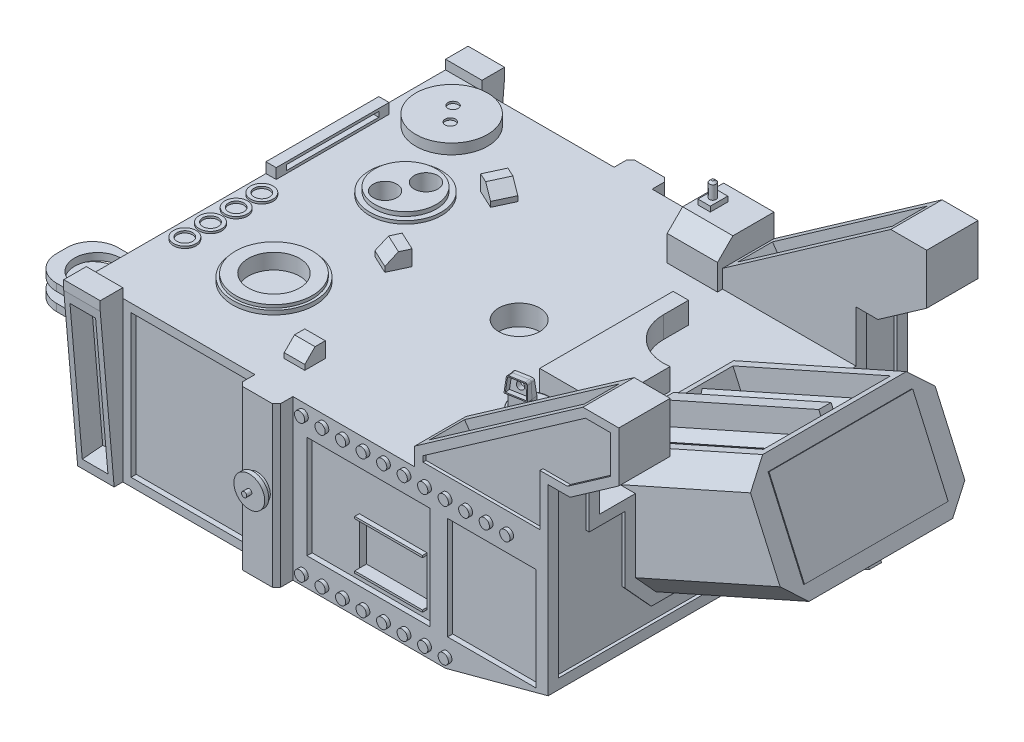
SolidWorks part; units mm, degrees
ref_plane "Ön Düzlem" through (0, 0, 0) normal (0, 0, 1) x (1, 0, 0)
ref_plane "Üst Düzlem" through (0, 0, 0) normal (0, 1, 0) x (1, 0, 0)
ref_plane "Sağ Düzlem" through (0, 0, 0) normal (1, 0, 0) x (0, 0, -1)
sketch "Sketch1" plane through (0, 0, 0) normal (0, 0, 1) x (1, 0, 0)
  line L1 (225, 77.5) -> (-225, 77.5)
  line L2 (225, 77.5) -> (225, -77.5)
  line L3 (225, -77.5) -> (-225, -77.5)
  line L4 (-225, 77.5) -> (-225, -77.5)
  line L5 (225, 77.5) -> (-225, -77.5) construction
  line L6 (225, -77.5) -> (-225, 77.5) construction
  point P0 (0, 0)
  dimension "D1" = 450
  dimension "D2" = 155
extrude "Boss-Extrude1" add sketch "Sketch1" along normal mid plane 350
sketch "Sketch2" plane through (0, 0, 175) normal (0, 0, 1) x (1, 0, 0)
  line L0 (-225, -77.5) -> (225, -77.5) construction
  line L1 (-189.45, -77.5) -> (-225, -77.5)
  line L2 (-189.45, -77.5) -> (-189.45, 86.5)
  line L3 (-189.45, 86.5) -> (-225, 86.5)
  line L4 (-225, -77.5) -> (-225, 86.5)
  line L5 (-225, 77.5) -> (-225, -77.5) construction
  dimension "D1" = 164
  dimension "D2" = 35.55
extrude "Boss-Extrude2" add sketch "Sketch2" along normal blind 22
sketch "Sketch3" plane through (0, 0, 175) normal (0, 0, 1) x (1, 0, 0)
  line L0 (225, 77.5) -> (-189.45, 77.5) construction
  line L1 (-23.725, -77.5) -> (-60.725, -77.5)
  line L2 (-23.725, -77.5) -> (-23.725, 77.5)
  line L3 (-23.725, 77.5) -> (-60.725, 77.5)
  line L4 (-60.725, -77.5) -> (-60.725, 77.5)
  line L5 (-23.725, -77.5) -> (-60.725, 77.5) construction
  line L6 (-23.725, 77.5) -> (-60.725, -77.5) construction
  line L7 (-189.45, 86.5) -> (-225, 86.5) construction
  line L8 (-207.225, 86.5) -> (-207.225, 0) construction
  line L9 (-207.225, 0) -> (0, 0) construction
  point P0 (-42.225, 0)
  dimension "D1" = 165
  dimension "D2" = 37
extrude "Boss-Extrude3" add sketch "Sketch3" along normal blind 16
sketch "Sketch4" plane through (0, 0, 175) normal (0, 0, 1) x (1, 0, 0)
  line L0 (125, -77.5) -> (225, -50.7051)
  line L1 (-23.725, -77.5) -> (225, -77.5) construction
  line L2 (225, -77.5) -> (225, 77.5) construction
  line L3 (225, -50.7051) -> (225, -77.5)
  line L4 (225, -77.5) -> (125, -77.5)
  dimension "D1" = 15
  dimension "D2" = 100
extrude "Cut-Extrude1" cut sketch "Sketch4" against normal through all
sketch "Sketch5" plane through (-225, 0, 0) normal (-1, 0, 0) x (0, 0, 1)
  line L0 (175, 77.5) -> (197, 77.5) construction
  line L1 (197, 86.5) -> (197, -77.5) construction
  line L2 (197, 77.5) -> (183.4393, -77.5)
  line L3 (183.4393, -77.5) -> (197, -77.5)
  line L4 (197, -77.5) -> (197, 77.5)
  dimension "D1" = 5
extrude "Cut-Extrude2" cut sketch "Sketch5" against normal up to surface (35.55 mm away) up to face at (-189.45, 19.1, 183.8)
chamfer "Chamfer1" distance 4 angle 45 2 edges at (-23.725, 0, 191) (-60.725, 0, 191)
sketch "Sketch6" plane through (0, 0, 191) normal (0, 0, 1) x (1, 0, 0)
  line L0 (-42.225, 77.5) -> (-42.225, 0) construction
  line L1 (-27.725, 77.5) -> (-56.725, 77.5) construction
  line L2 (-42.225, 0) -> (0, 0) construction
  circle A0 centre (-42.225, 0) radius 12.5
  dimension "D1" = 25
extrude "Boss-Extrude4" add sketch "Sketch6" along normal blind 4
sketch "Sketch7" plane through (0, 0, 195) normal (0, 0, 1) x (1, 0, 0)
  circle A0 centre (-42.225, 0) radius 15
  dimension "D1" = 30
extrude "Boss-Extrude5" add sketch "Sketch7" along normal blind 4
sketch "Sketch8" plane through (0, 0, 199) normal (0, 0, 1) x (1, 0, 0)
  circle A0 centre (-42.225, 0) radius 2.5
  dimension "D1" = 5
extrude "Boss-Extrude6" add sketch "Sketch8" along normal blind 5
sketch "Sketch9" plane through (0, 0, 175) normal (0, 0, 1) x (1, 0, 0)
  line L0 (50, 0) -> (170, 0) construction
  line L4 (0, 0) -> (50, 0) construction
  line L5 (110, -50) -> (-10, -50)
  line L6 (110, -50) -> (110, 50)
  line L7 (110, 50) -> (-10, 50)
  line L8 (-68.725, -69.5) -> (-68.725, 69.5)
  line L9 (-68.725, 69.5) -> (-181.45, 69.5)
  line L10 (-181.45, 69.5) -> (-181.45, -69.5)
  line L11 (-181.45, -69.5) -> (-68.725, -69.5)
  line L12 (-68.725, -69.5) -> (-68.725, 69.5)
  line L13 (-68.725, 69.5) -> (-181.45, 69.5)
  line L14 (-181.45, 69.5) -> (-181.45, -69.5)
  line L15 (-181.45, -69.5) -> (-68.725, -69.5)
  line L16 (-10, -50) -> (-10, 50)
  line L17 (110, -50) -> (-10, 50) construction
  line L18 (110, 50) -> (-10, -50) construction
  line L20 (213, -50) -> (127, -50)
  line L21 (213, -50) -> (213, 50)
  line L22 (213, 50) -> (127, 50)
  line L23 (127, -50) -> (127, 50)
  line L24 (213, -50) -> (127, 50) construction
  line L25 (213, 50) -> (127, -50) construction
  point P0 (50, 0)
  point P13 (170, 0)
  dimension "D2" = 50
  dimension "D3" = 120
  dimension "D4" = 100
  dimension "D5" = 86
  dimension "D6" = 120
  dimension "D1" = 8
extrude "Cut-Extrude3" cut sketch "Sketch9" against normal blind 5
sketch "Sketch10" plane through (0, 0, 170) normal (0, 0, 1) x (1, 0, 0)
  line L0 (-10, -50) -> (110, -50) construction
  line L1 (102, -40) -> (36, -40)
  line L2 (102, -40) -> (102, 4)
  line L3 (102, 4) -> (36, 4)
  line L4 (36, -40) -> (36, 4)
  line L5 (102, -40) -> (36, 4) construction
  line L6 (102, 4) -> (36, -40) construction
  line L7 (110, -50) -> (110, 50) construction
  point P0 (69, -18)
  dimension "D1" = 10
  dimension "D2" = 44
  dimension "D3" = 8
  dimension "D4" = 66
extrude "Cut-Extrude4" cut sketch "Sketch10" against normal blind 7
sketch "Sketch12" plane through (0, 0, 170) normal (0, 0, 1) x (1, 0, 0)
  line L0 (102, -40) -> (102, 4) construction
  line L1 (36, 4) -> (102, 4)
  line L2 (36, 4) -> (36, 6)
  line L3 (36, 6) -> (102, 6)
  line L4 (102, 4) -> (102, 6)
  line L5 (36, -40) -> (102, -40)
  line L6 (36, -40) -> (36, -42)
  line L7 (36, -42) -> (102, -42)
  line L8 (102, -40) -> (102, -42)
  line L9 (102, -40) -> (102, 4) construction
  dimension "D1" = 2
  dimension "D2" = 2
extrude "Boss-Extrude7" add sketch "Sketch12" along normal blind 4.5
sketch "Sketch13" plane through (0, -16.5156, 188.7747) normal (0, -0.0872, 0.9962) x (1, 0, 0)
  line L0 (-207.225, 94.3748) -> (-207.225, -61.2173) construction
  line L1 (-219.725, 85.5787) -> (-194.725, 85.5787)
  line L2 (-219.725, 85.5787) -> (-219.725, -52.4213)
  line L3 (-219.725, -52.4213) -> (-194.725, -52.4213)
  line L4 (-194.725, 85.5787) -> (-194.725, -52.4213)
  line L5 (-189.45, 94.3748) -> (-225, 94.3748) construction
  line L6 (-189.45, -61.2173) -> (-225, -61.2173) construction
  line L7 (-225, 16.5787) -> (-189.45, 16.5787) construction
  line L8 (-225, 94.3748) -> (-225, -61.2173) construction
  line L9 (-189.45, -61.2173) -> (-189.45, 94.3748) construction
  point P10 (-207.225, 85.5787)
  point P17 (-219.725, 16.5787)
  dimension "D1" = 25
  dimension "D2" = 138
extrude "Cut-Extrude5" cut sketch "Sketch13" against normal blind 20
mirror "Mirror1" about plane through (0, 0, 0) normal (0, 0, 1) of "Cut-Extrude5", "Boss-Extrude7", "Cut-Extrude4", "Cut-Extrude3", "Boss-Extrude6", "Boss-Extrude5", "Boss-Extrude4", "Chamfer1", "Cut-Extrude2", "Boss-Extrude3", "Boss-Extrude2"
sketch "Sketch14" plane through (-225, 0, 0) normal (-1, 0, 0) x (0, 0, 1)
  line L0 (0, 0) -> (-190.2196, 0) construction
  line L1 (-197, 77.5) -> (-183.4393, -77.5) construction
  line L2 (0, 0) -> (190.2196, 0) construction
  line L3 (197, 77.5) -> (183.4393, -77.5) construction
  line L5 (-65, 60) -> (-170, 60)
  line L6 (-65, 60) -> (-65, -60)
  line L7 (-65, -60) -> (-170, -60)
  line L8 (-170, 60) -> (-170, -60)
  line L9 (-65, 60) -> (-170, -60) construction
  line L10 (-65, -60) -> (-170, 60) construction
  point P5 (-117.5, 0)
  dimension "D1" = 105
  dimension "D2" = 120
  dimension "D3" = 170
extrude "Cut-Extrude6" cut sketch "Sketch14" against normal blind 15
sketch "Sketch15" plane through (-210, 0, 0) normal (-1, 0, 0) x (0, 0, 1)
  line L0 (-164.8939, -60) -> (-65, -60) construction
  line L1 (-170, 60) -> (-170, -60) construction
  circle A0 centre (-143, -5) radius 7.5
  dimension "D3" = 15
  dimension "D1" = 55
  dimension "D2" = 27
extrude "Boss-Extrude8" add sketch "Sketch15" along normal blind 15
sketch "Sketch16" plane through (-225, 0, 0) normal (-1, 0, 0) x (0, 0, 1)
  line L0 (0, 0) -> (99, 0) construction
  circle A0 centre (99, 0) radius 48.5
  dimension "D2" = 97
  dimension "D1" = 99
extrude "Boss-Extrude9" add sketch "Sketch16" along normal blind 10
sketch "Sketch17" plane through (-235, 0, 0) normal (-1, 0, 0) x (0, 0, 1)
  circle A0 centre (99, 0) radius 35
  dimension "D1" = 70
extrude "Boss-Extrude11" add sketch "Sketch17" along normal blind 5 contours A0
sketch "Sketch18" plane through (-240, 0, 0) normal (-1, 0, 0) x (0, 0, 1)
  line L0 (0, 0) -> (134, 0) construction
  line L1 (99, 0) -> (99, 35) construction
  line L2 (129, 5) -> (69, 5)
  line L3 (129, 5) -> (129, 12)
  line L4 (129, 12) -> (69, 12)
  line L5 (69, 5) -> (69, 12)
  line L6 (129, 5) -> (69, 12) construction
  line L7 (129, 12) -> (69, 5) construction
  line L8 (129, -12) -> (69, -12)
  line L9 (69, -5) -> (69, -12)
  line L10 (129, -5) -> (69, -5)
  line L11 (129, -5) -> (129, -12)
  circle A0 centre (99, 0) radius 35 construction
  circle A1 centre (99, 0) radius 35 construction
  point P6 (99, 8.5)
  dimension "D1" = 7
  dimension "D2" = 60
  dimension "D3" = 5
extrude "Boss-Extrude12" add sketch "Sketch18" along normal blind 85
fillet "Fillet4" radius 25 4 edges at (-325, -8.5, 129) (-325, 8.5, 129) (-325, 8.5, 69) (-325, -8.5, 69)
sketch "Sketch19" plane through (0, -12, 0) normal (0, -1, 0) x (1, 0, 0)
  line L0 (-240, 99) -> (-325, 99) construction
  line L1 (-240, 69) -> (-240, 129) construction
  line L2 (-325, 94) -> (-325, 104) construction
  line L3 (-240, 134) -> (-240, 64) construction
  circle A0 centre (-290, 99) radius 22.5
  dimension "D2" = 45
  dimension "D1" = 50
extrude "Cut-Extrude7" cut sketch "Sketch19" against normal blind 85
sketch "Sketch20" plane through (0, 77.5, 0) normal (0, 1, 0) x (1, 0, 0)
  line L0 (-225, -175) -> (-225, 175) construction
  line L1 (-225, 110) -> (-215, 110)
  line L2 (-225, 110) -> (-225, 0)
  line L3 (-225, 0) -> (-215, 0)
  line L4 (-215, 110) -> (-215, 0)
  dimension "D1" = 110
  dimension "D2" = 10
extrude "Boss-Extrude13" add sketch "Sketch20" along normal blind 10
sketch "Sketch21" plane through (-225, 0, 0) normal (-1, 0, 0) x (0, 0, 1)
  line L0 (-110, 82.5) -> (0, 82.5) construction
  line L1 (-110, 87.5) -> (-110, 77.5) construction
  line L2 (0, 87.5) -> (0, 77.5) construction
  line L4 (-10, 85) -> (-100, 85)
  line L5 (-10, 85) -> (-10, 80)
  line L6 (-10, 80) -> (-100, 80)
  line L7 (-100, 85) -> (-100, 80)
  line L8 (-10, 85) -> (-100, 80) construction
  line L9 (-10, 80) -> (-100, 85) construction
  point P6 (-55, 82.5)
  dimension "D1" = 90
  dimension "D2" = 5
extrude "Cut-Extrude8" cut sketch "Sketch21" against normal blind 10
sketch "Sketch22" plane through (-225, 0, 0) normal (-1, 0, 0) x (0, 0, 1)
  line L1 (47.5, 0.9) -> (-47.5, 0.9)
  line L2 (47.5, 0.9) -> (47.5, -31.1)
  line L3 (47.5, -31.1) -> (-47.5, -31.1)
  line L4 (-47.5, 0.9) -> (-47.5, -31.1)
  line L5 (47.5, 0.9) -> (-47.5, -31.1) construction
  line L6 (47.5, -31.1) -> (-47.5, 0.9) construction
  point P0 (0, -15.1)
  dimension "D1" = 95
  dimension "D2" = 32
  dimension "D3" = 15.1
extrude "Cut-Extrude9" cut sketch "Sketch22" against normal blind 5
sketch "Sketch23" plane through (0, 77.5, 0) normal (0, 1, 0) x (1, 0, 0)
  line L0 (-42.225, 204) -> (-42.225, 0) construction
  line L1 (-39.725, 204) -> (-44.725, 204) construction
  line L2 (-42.225, 0) -> (21.775, 0) construction
  circle A0 centre (21.775, 0) radius 20
  dimension "D2" = 40
  dimension "D1" = 64
extrude "Cut-Extrude10" cut sketch "Sketch23" against normal blind 20
sketch "Sketch24" plane through (0, 0, 0) normal (0, 0, 1) x (1, 0, 0)
  line L0 (0, 50) -> (99, 50) construction
  line L1 (110, 50) -> (-10, 50) construction
  line L2 (0, 0) -> (0, 50) construction
  line L3 (99, 50) -> (144.1478, -51.4035)
  line L4 (144.1478, -51.4035) -> (374.1478, 50.9991)
  line L5 (374.1478, 50.9991) -> (329, 152.4026)
  line L6 (329, 152.4026) -> (99, 50)
  dimension "D1" = 99
  dimension "D2" = 111
  dimension "D3" = 156
  dimension "D4" = 230
extrude "Boss-Extrude14" add sketch "Sketch24" along normal mid plane 180
chamfer "Chamfer3" distance 20 angle 45 4 edges at (299.5739, 17.7966, 90) (244.883, 114.9513, 90) (299.5739, 17.7966, -90) (244.883, 114.9513, -90)
sketch "Sketch25" plane through (-2.2006, 4.9426, 0) normal (-0.4067, 0.9135, 0) x (0.9135, 0.4067, 0)
  line L8 (186.3891, 62) -> (186.3891, -62)
  line L9 (186.3891, -62) -> (354.5442, -62)
  line L10 (354.5442, -62) -> (354.5442, 62)
  line L11 (354.5442, 62) -> (186.3891, 62)
  line L12 (186.3891, 62) -> (186.3891, -62)
  line L13 (186.3891, -62) -> (354.5442, -62)
  line L14 (354.5442, -62) -> (354.5442, 62)
  line L15 (354.5442, 62) -> (186.3891, 62)
  dimension "D1" = 8
extrude "Cut-Extrude11" cut sketch "Sketch25" against normal up to surface (111 mm away) up to face at (299.5739, 17.7966, 0)
sketch "Sketch26" plane through (170.275, 75.8113, 0) normal (0.9135, 0.4067, 0) x (0, 0, -1)
  line L0 (0, 5.4103) -> (0, -105.5897) construction
  line L1 (62, 5.4103) -> (-62, 5.4103) construction
  line L4 (-62, -105.5897) -> (62, -105.5897) construction
  circle A0 centre (0, -50.0897) radius 32.5
  dimension "D1" = 65
extrude "Boss-Extrude15" add sketch "Sketch26" along normal up to surface (168.155 mm away) up to face at (344.2655, 98.4469, 0)
ref_plane "Plane1" through (-2.2006, 4.9426, 0) normal (-0.4067, 0.9135, 0) x (0.9135, 0.4067, 0)
sketch "Sketch27" plane through (-2.2006, 4.9426, 0) normal (-0.4067, 0.9135, 0) x (0.9135, 0.4067, 0)
  line L0 (186.3891, 0) -> (354.5442, 0) construction
  line L1 (186.3891, -32.5) -> (186.3891, 32.5) construction
  line L2 (354.5442, -62) -> (354.5442, 62) construction
  line L3 (270.4667, 0) -> (270.4667, -62) construction
  line L4 (186.3891, -62) -> (354.5442, -62) construction
  line L6 (354.5442, -6) -> (186.3891, -6)
  line L7 (354.5442, -6) -> (354.5442, 6)
  line L8 (354.5442, 6) -> (186.3891, 6)
  line L9 (186.3891, -6) -> (186.3891, 6)
  line L10 (354.5442, -6) -> (186.3891, 6) construction
  line L11 (354.5442, 6) -> (186.3891, -6) construction
  dimension "D1" = 12
extrude "Boss-Extrude17" add sketch "Sketch27" along normal blind 5 and the other way up to surface contours L6 L9 L8 L7 other way up to face at (203.8672, 0.3619, 0)
pattern_circular "CirPattern1" count 10 over 360 about axis through (20.3733, -45.7592, 0) along (0.9135, 0.4067, 0) of "Boss-Extrude17"
sketch "Sketch28" plane through (331.2006, 147.46, 0) normal (0.9135, 0.4067, 0) x (0, 0, -1)
  line L0 (-90, -50.0897) -> (90, -50.0897) construction
  line L1 (-90, -85.5897) -> (-90, -14.5897) construction
  line L2 (90, -85.5897) -> (90, -14.5897) construction
  line L3 (0, 5.4103) -> (0, -105.5897) construction
  line L4 (6, 5.4103) -> (-6, 5.4103) construction
  line L5 (-70, -105.5897) -> (70, -105.5897) construction
  line L7 (70, -92.5897) -> (-70, -92.5897)
  line L8 (70, -92.5897) -> (70, -7.5897)
  line L9 (70, -7.5897) -> (-70, -7.5897)
  line L10 (-70, -92.5897) -> (-70, -7.5897)
  line L11 (70, -92.5897) -> (-70, -7.5897) construction
  line L12 (70, -7.5897) -> (-70, -92.5897) construction
  point P12 (0, -50.0897)
  dimension "D1" = 140
  dimension "D2" = 85
extrude "Boss-Extrude18" add sketch "Sketch28" along normal blind 1
sketch "Sketch29" plane through (0, 0, 175) normal (0, 0, 1) x (1, 0, 0)
  line L0 (-23.725, 67) -> (225, 67) construction
  line L1 (-23.725, -77.5) -> (-23.725, 77.5) construction
  line L2 (225, -50.7051) -> (225, 77.5) construction
  line L3 (225, 77.5) -> (-23.725, 77.5) construction
  line L4 (-27.725, -77.5) -> (-27.725, 77.5) construction
  line L5 (-13.725, 67) -> (-13.725, -67) construction
  line L6 (-23.725, -67) -> (164.1865, -67) construction
  line L7 (225, -50.7051) -> (125, -77.5) construction
  line L8 (-23.725, -77.5) -> (125, -77.5) construction
  circle A0 centre (-13.725, 67) radius 5
  circle A1 centre (6.275, 67) radius 5
  circle A2 centre (26.275, 67) radius 5
  circle A3 centre (46.275, 67) radius 5
  circle A4 centre (66.275, 67) radius 5
  circle A5 centre (86.275, 67) radius 5
  circle A6 centre (106.275, 67) radius 5
  circle A7 centre (126.275, 67) radius 5
  circle A8 centre (146.275, 67) radius 5
  circle A9 centre (166.275, 67) radius 5
  circle A10 centre (186.275, 67) radius 5
  circle A11 centre (-13.725, -67) radius 5
  circle A12 centre (6.275, -67) radius 5
  circle A13 centre (26.275, -67) radius 5
  circle A14 centre (46.275, -67) radius 5
  circle A15 centre (66.275, -67) radius 5
  circle A16 centre (86.275, -67) radius 5
  circle A17 centre (106.275, -67) radius 5
  circle A18 centre (126.275, -67) radius 5
  dimension "D3" = 10
  dimension "D7" = 10
  dimension "D1" = 10.5
  dimension "D2" = 14
  dimension "D5" = 20
  dimension "D6" = 10.5
  dimension "D9" = 20
  dimension "D4" = 11
  dimension "D8" = 8
extrude "Boss-Extrude19" add sketch "Sketch29" along normal blind 3.5
mirror "Mirror2" about plane through (0, 0, 0) normal (0, 0, 1) of "Boss-Extrude19"
sketch "Sketch30" plane through (-225, 0, 0) normal (-1, 0, 0) x (0, 0, 1)
  line L0 (195.6877, 62.5) -> (-40.6, 62.5) construction
  line L1 (197, 77.5) -> (183.4393, -77.5) construction
  line L2 (175, 77.5) -> (0, 77.5) construction
  line L3 (197, 86.5) -> (197, 77.5) construction
  circle A0 centre (175.4, 62.5) radius 5.5
  circle A1 centre (157.4, 62.5) radius 5.5
  circle A2 centre (139.4, 62.5) radius 5.5
  circle A3 centre (121.4, 62.5) radius 5.5
  circle A4 centre (103.4, 62.5) radius 5.5
  circle A5 centre (85.4, 62.5) radius 5.5
  circle A6 centre (67.4, 62.5) radius 5.5
  circle A7 centre (49.4, 62.5) radius 5.5
  circle A8 centre (31.4, 62.5) radius 5.5
  circle A9 centre (13.4, 62.5) radius 5.5
  circle A10 centre (-4.6, 62.5) radius 5.5
  circle A11 centre (-22.6, 62.5) radius 5.5
  circle A12 centre (-40.6, 62.5) radius 5.5
  dimension "D3" = 11
  dimension "D1" = 15
  dimension "D2" = 21.6
  dimension "D5" = 18
  dimension "D4" = 13
extrude "Boss-Extrude20" add sketch "Sketch30" along normal blind 2.5
sketch "Sketch31" plane through (0, 0, 175) normal (0, 0, 1) x (1, 0, 0)
  line L0 (225, 77.5) -> (95, 77.5)
  line L1 (225, 77.5) -> (-23.725, 77.5) construction
  line L2 (95, 77.5) -> (95, 95.0521)
  line L3 (95, 95.0521) -> (258.8304, 209.7674)
  line L4 (258.8304, 209.7674) -> (293.8304, 209.7674)
  line L5 (293.8304, 209.7674) -> (293.8304, 160.7674)
  line L6 (293.8304, 160.7674) -> (246.3196, 127.5)
  line L7 (246.3196, 127.5) -> (225, 127.5)
  line L8 (225, 127.5) -> (225, 77.5)
  dimension "D1" = 200
  dimension "D2" = 35
  dimension "D3" = 50
  dimension "D4" = 58
  dimension "D5" = 49
  dimension "D6" = 130
  dimension "D7" = 145
extrude "Boss-Extrude21" add sketch "Sketch31" against normal blind 50
sketch "Sketch32" plane through (-13.4059, 19.1455, 0) normal (-0.5736, 0.8192, 0) x (0.8192, 0.5736, 0)
  line L8 (140.3391, -167) -> (324.3391, -167)
  line L9 (324.3391, -167) -> (324.3391, -133)
  line L10 (324.3391, -133) -> (140.3391, -133)
  line L11 (140.3391, -133) -> (140.3391, -167)
  line L12 (140.3391, -167) -> (324.3391, -167)
  line L13 (324.3391, -167) -> (324.3391, -133)
  line L14 (324.3391, -133) -> (140.3391, -133)
  line L15 (140.3391, -133) -> (140.3391, -167)
  dimension "D1" = 8
extrude "Cut-Extrude12" cut sketch "Sketch32" against normal blind 25
sketch "Sketch33" plane through (0, 0, 175) normal (0, 0, 1) x (1, 0, 0)
  line L0 (95, 77.5) -> (95, 95.0521) construction
  line L1 (95, 95.0521) -> (258.8304, 209.7674) construction
  line L2 (258.8304, 209.7674) -> (293.8304, 209.7674) construction
  line L3 (293.8304, 209.7674) -> (293.8304, 160.7674) construction
  line L4 (293.8304, 160.7674) -> (246.3196, 127.5) construction
  line L5 (246.3196, 127.5) -> (293.8304, 160.7674) construction
  line L6 (246.3196, 127.5) -> (225, 127.5) construction
  line L7 (225, 127.5) -> (225, 77.5) construction
  line L8 (225, -50.7051) -> (225, 127.5) construction
  line L9 (225, 77.5) -> (95, 77.5) construction
  line L10 (103, 90.8876) -> (261.3528, 201.7674)
  line L11 (261.3528, 201.7674) -> (285.8304, 201.7674)
  line L12 (285.8304, 201.7674) -> (285.8304, 164.932)
  line L13 (285.8304, 164.932) -> (243.7972, 135.5)
  line L14 (243.7972, 135.5) -> (217, 135.5)
  line L15 (217, 135.5) -> (217, 85.5)
  line L16 (217, 85.5) -> (103, 85.5)
  line L17 (103, 85.5) -> (103, 90.8876)
  dimension "D1" = 8
extrude "Cut-Extrude13" cut sketch "Sketch33" against normal blind 3
mirror "Mirror3" about plane through (0, 0, 0) normal (0, 0, 1) of "Boss-Extrude21", "Cut-Extrude12", "Cut-Extrude13"
sketch "Sketch34" plane through (225, 0, 0) normal (1, 0, 0) x (0, 0, -1)
  line L40 (16, -30.879) -> (-16, -30.879)
  line L41 (-16, -30.879) -> (-16, -25.4058)
  line L42 (-16, -25.4058) -> (-62, -25.4058)
  line L43 (-62, -25.4058) -> (-74.4092, -25.4058)
  line L44 (-74.4092, -25.4058) -> (-100, 2.6069)
  line L45 (-100, 2.6069) -> (-100, 67.5)
  line L46 (-100, 67.5) -> (-135, 67.5)
  line L47 (-135, 67.5) -> (-135, 117.5)
  line L48 (-135, 117.5) -> (-165, 117.5)
  line L49 (-165, 117.5) -> (-165, -40.7051)
  line L50 (-165, -40.7051) -> (165, -40.7051)
  line L51 (165, -40.7051) -> (165, 117.5)
  line L52 (165, 117.5) -> (135, 117.5)
  line L53 (135, 117.5) -> (135, 67.5)
  line L54 (135, 67.5) -> (100, 67.5)
  line L55 (100, 67.5) -> (100, 2.6069)
  line L56 (100, 2.6069) -> (74.4092, -25.4058)
  line L57 (74.4092, -25.4058) -> (62, -25.4058)
  line L58 (62, -25.4058) -> (16, -25.4058)
  line L59 (16, -25.4058) -> (16, -30.879)
  line L60 (16, -30.879) -> (-16, -30.879)
  line L61 (-16, -30.879) -> (-16, -25.4058)
  line L62 (-16, -25.4058) -> (-62, -25.4058)
  line L63 (-62, -25.4058) -> (-74.4092, -25.4058)
  line L64 (-74.4092, -25.4058) -> (-100, 2.6069)
  line L65 (-100, 2.6069) -> (-100, 67.5)
  line L66 (-100, 67.5) -> (-135, 67.5)
  line L67 (-135, 67.5) -> (-135, 117.5)
  line L68 (-135, 117.5) -> (-165, 117.5)
  line L69 (-165, 117.5) -> (-165, -40.7051)
  line L70 (-165, -40.7051) -> (165, -40.7051)
  line L71 (165, -40.7051) -> (165, 117.5)
  line L72 (165, 117.5) -> (135, 117.5)
  line L73 (135, 117.5) -> (135, 67.5)
  line L74 (135, 67.5) -> (100, 67.5)
  line L75 (100, 67.5) -> (100, 2.6069)
  line L76 (100, 2.6069) -> (74.4092, -25.4058)
  line L77 (74.4092, -25.4058) -> (62, -25.4058)
  line L78 (62, -25.4058) -> (16, -25.4058)
  line L79 (16, -25.4058) -> (16, -30.879)
  dimension "D1" = 10
extrude "Cut-Extrude14" cut sketch "Sketch34" against normal blind 3
sketch "Sketch35" plane through (0, 77.5, 0) normal (0, 1, 0) x (1, 0, 0)
  line L0 (-225, 110) -> (-225, 0) construction
  circle A0 centre (-175, 131) radius 35
  dimension "D3" = 70
  dimension "D1" = 50
  dimension "D2" = 44
extrude "Boss-Extrude22" add sketch "Sketch35" along normal blind 10
sketch "Sketch36" plane through (0, 87.5, 0) normal (0, 1, 0) x (1, 0, 0)
  line L0 (-210, 131) -> (-140, 131) construction
  line L1 (-175, 96) -> (-175, 166) construction
  circle A0 centre (-175, 131) radius 35 construction
  circle A1 centre (-175, 131) radius 35 construction
  circle A2 centre (-181.33, 138.66) radius 5
  circle A3 centre (-168.67, 123.34) radius 5
  dimension "D2" = 6.33
  dimension "D4" = 7.66
  dimension "D5" = 10
  dimension "D1" = 7.66
  dimension "D3" = 6.33
extrude "Cut-Extrude15" cut sketch "Sketch36" against normal blind 2
sketch "Sketch37" plane through (0, 77.5, 0) normal (0, 1, 0) x (1, 0, 0)
  line L1 (95, 175) -> (46, 175)
  line L2 (95, 175) -> (95, 120)
  line L3 (95, 120) -> (46, 120)
  line L4 (46, 175) -> (46, 120)
  dimension "D1" = 49
  dimension "D2" = 55
extrude "Boss-Extrude23" add sketch "Sketch37" along normal blind 40 contours L3 L4 L1 L2
chamfer "Chamfer4" distance 15 angle 45 1 edges at (70.5, 117.5, -120)
sketch "Sketch38" plane through (0, 117.5, 0) normal (0, 1, 0) x (1, 0, 0)
  line L0 (46, 175) -> (46, 120) construction
  line L1 (64, 161) -> (52, 161)
  line L2 (64, 161) -> (64, 144)
  line L3 (64, 144) -> (52, 144)
  line L4 (52, 161) -> (52, 144)
  line L5 (64, 161) -> (52, 144) construction
  line L6 (64, 144) -> (52, 161) construction
  line L8 (46, 175) -> (-23.725, 175) construction
  point P0 (58, 152.5)
  dimension "D1" = 12
  dimension "D2" = 17
  dimension "D3" = 6
  dimension "D4" = 14
extrude "Boss-Extrude24" add sketch "Sketch38" along normal blind 5
sketch "Sketch39" plane through (0, 122.5, 0) normal (0, 1, 0) x (1, 0, 0)
  line L0 (52, 152.5) -> (64, 152.5) construction
  line L1 (52, 161) -> (52, 144) construction
  line L2 (64, 144) -> (64, 161) construction
  line L3 (58, 161) -> (58, 144) construction
  line L4 (64, 161) -> (52, 161) construction
  line L5 (52, 144) -> (64, 144) construction
  circle A0 centre (58, 152.5) radius 3.25
  dimension "D1" = 6.5
extrude "Boss-Extrude25" add sketch "Sketch39" along normal blind 15
chamfer "Chamfer5" distance 2 angle 45 1 edges at (58, 137.5, -149.25)
sketch "Sketch40" plane through (0, 77.5, 0) normal (0, 1, 0) x (1, 0, 0)
  line L0 (155.766, -52) -> (93.766, -52)
  line L1 (93.766, -52) -> (93.766, 78)
  line L2 (93.766, 78) -> (108.766, 78)
  line L3 (108.766, 78) -> (108.766, 53.8519)
  line L4 (155.766, -52) -> (155.766, 13)
  line L5 (160.766, 70) -> (160.766, -70) construction
  arc A0 (108.766, 53.8519) -> (155.766, 13) centre (150.02, 53.8519) ccw
  dimension "D4" = 41.254
  dimension "D1" = 130
  dimension "D2" = 62
  dimension "D3" = 5
  dimension "D5" = 65
  dimension "D6" = 15
  dimension "D7" = 13
extrude "Boss-Extrude26" add sketch "Sketch40" along normal blind 21
sketch "Sketch42" plane through (0, 77.5, 0) normal (0, 1, 0) x (1, 0, 0)
  line L0 (225, -125) -> (225, -90) construction
  line L1 (95, -125) -> (225, -125) construction
  circle A0 centre (130, -97) radius 20
  dimension "D3" = 40
  dimension "D1" = 95
  dimension "D2" = 28
extrude "Boss-Extrude27" add sketch "Sketch42" along normal blind 3
sketch "Sketch43" plane through (0, 80.5, 0) normal (0, 1, 0) x (1, 0, 0)
  line L1 (130, -70.7306) -> (107.25, -83.8653)
  line L2 (107.25, -83.8653) -> (107.25, -110.1347)
  line L3 (107.25, -110.1347) -> (130, -123.2694)
  line L4 (130, -123.2694) -> (152.75, -110.1347)
  line L5 (152.75, -110.1347) -> (152.75, -83.8653)
  line L6 (152.75, -83.8653) -> (130, -70.7306)
  circle A0 centre (130, -97) radius 22.75 construction
  dimension "D1" = 45.5
extrude "Boss-Extrude28" add sketch "Sketch43" along normal blind 6
sketch "Sketch44" plane through (0, 86.5, 0) normal (0, 1, 0) x (1, 0, 0)
  line L12 (149.75, -85.5973) -> (130, -74.1947)
  line L13 (130, -74.1947) -> (110.25, -85.5973)
  line L14 (110.25, -85.5973) -> (110.25, -108.4027)
  line L15 (110.25, -108.4027) -> (130, -119.8053)
  line L16 (130, -119.8053) -> (149.75, -108.4027)
  line L17 (149.75, -108.4027) -> (149.75, -85.5973)
  line L18 (149.75, -85.5973) -> (130, -74.1947)
  line L19 (130, -74.1947) -> (110.25, -85.5973)
  line L20 (110.25, -85.5973) -> (110.25, -108.4027)
  line L21 (110.25, -108.4027) -> (130, -119.8053)
  line L22 (130, -119.8053) -> (149.75, -108.4027)
  line L23 (149.75, -108.4027) -> (149.75, -85.5973)
  dimension "D1" = 3
extrude "Cut-Extrude17" cut sketch "Sketch44" against normal blind 4
sketch "Sketch45" plane through (0, 82.5, 0) normal (0, 1, 0) x (1, 0, 0)
  line L0 (110.25, -97) -> (149.75, -97) construction
  line L1 (110.25, -85.5973) -> (110.25, -108.4027) construction
  line L2 (149.75, -108.4027) -> (149.75, -85.5973) construction
  circle A0 centre (130, -97) radius 12.5
  dimension "D1" = 25
extrude "Boss-Extrude29" add sketch "Sketch45" along normal blind 20
sketch "Sketch46" plane through (0, 102.5, 0) normal (0, 1, 0) x (1, 0, 0)
  circle A0 centre (130, -97) radius 18
  dimension "D1" = 36
extrude "Boss-Extrude30" add sketch "Sketch46" along normal blind 5
sketch "Sketch47" plane through (0, 107.5, 0) normal (0, 1, 0) x (1, 0, 0)
  line L0 (112, -97) -> (148, -97) construction
  line L1 (119.631, -103.7821) -> (139.3271, -100.3091)
  line L2 (139.3271, -100.3091) -> (140.369, -106.2179)
  line L3 (140.369, -106.2179) -> (120.6729, -109.6909)
  line L4 (120.6729, -109.6909) -> (119.631, -103.7821)
  line L5 (120.6729, -109.6909) -> (139.3271, -100.3091) construction
  line L6 (119.631, -103.7821) -> (140.369, -106.2179) construction
  circle A0 centre (130, -97) radius 18 construction
  point P7 (130, -105)
  point P10 (130, -97)
  dimension "D1" = 10
  dimension "D2" = 6
  dimension "D3" = 20
  dimension "D4" = 8
extrude "Boss-Extrude31" add sketch "Sketch47" along normal blind 15
sketch "Sketch48" plane through (0, 122.5, 0) normal (0, 1, 0) x (1, 0, 0)
  line L4 (119.631, -103.7821) -> (120.6729, -109.6909)
  line L5 (120.6729, -109.6909) -> (140.369, -106.2179)
  line L6 (140.369, -106.2179) -> (139.3271, -100.3091)
  line L7 (139.3271, -100.3091) -> (119.631, -103.7821)
  line L8 (119.631, -103.7821) -> (120.6729, -109.6909)
  line L9 (120.6729, -109.6909) -> (140.369, -106.2179)
  line L10 (140.369, -106.2179) -> (139.3271, -100.3091)
  line L11 (139.3271, -100.3091) -> (119.631, -103.7821)
  dimension "D1" = 0
extrude "Boss-Extrude32" add sketch "Sketch48" along normal blind 15 draft 5
sketch "Sketch49" plane through (24.0738, 12.129, 136.5291) normal (0.173, 0.0872, 0.9811) x (0.9849, -0.0153, -0.1723)
  line L0 (107.8452, 127.5221) -> (108.0765, 112.4666) construction
  line L1 (99.1585, 127.3886) -> (116.5318, 127.6556) construction
  line L2 (98.0777, 112.3129) -> (118.0754, 112.6202) construction
  circle A0 centre (107.9609, 119.9943) radius 3.5
  dimension "D1" = 7
extrude "Cut-Extrude18" cut sketch "Sketch49" against normal blind 15
chamfer "Chamfer6" distance 2 angle 45 6 edges at (139.875, 86.5, 79.896) (149.75, 86.5, 97) (139.875, 86.5, 114.104) (120.125, 86.5, 114.104) (110.25, 86.5, 97) (120.125, 86.5, 79.896)
fillet "Fillet5" radius 2 2 edges at (130, 102.5, 115) (130, 107.5, 115)
fillet "Fillet6" radius 2 2 edges at (138.5557, 137.5, 103.4914) (121.4443, 137.5, 106.5086)
sketch "Sketch50" plane through (24.0738, 12.129, 136.5291) normal (0.173, 0.0872, 0.9811) x (0.9849, -0.0153, -0.1723)
  line L8 (116.9692, 113.6034) -> (115.7249, 125.7235)
  line L9 (114.7147, 126.6275) -> (101.0063, 126.4169)
  line L10 (100.0244, 125.4822) -> (99.1532, 113.3296)
  line L11 (99.1532, 113.3296) -> (116.9692, 113.6034)
  line L12 (116.9692, 113.6034) -> (115.7249, 125.7235)
  line L13 (114.7147, 126.6275) -> (101.0063, 126.4169)
  line L14 (100.0244, 125.4822) -> (99.1532, 113.3296)
  line L15 (99.1532, 113.3296) -> (116.9692, 113.6034)
  line L16 (118.0754, 112.6202) -> (116.7197, 125.8256)
  line L17 (114.6994, 127.6274) -> (100.991, 127.4168)
  line L18 (99.027, 125.5537) -> (98.0777, 112.3129)
  line L19 (98.0777, 112.3129) -> (118.0754, 112.6202)
  line L20 (118.0754, 112.6202) -> (116.7197, 125.8256)
  line L21 (114.6994, 127.6274) -> (100.991, 127.4168)
  line L22 (99.027, 125.5537) -> (98.0777, 112.3129)
  line L23 (98.0777, 112.3129) -> (118.0754, 112.6202)
  ellipse E4 centre (114.7302, 125.62) end of major axis (114.6994, 127.6274) minor radius 2 (116.7197, 125.8256) -> (114.6994, 127.6274) ccw
  ellipse E5 centre (101.0218, 125.4094) end of major axis (100.991, 127.4168) minor radius 2 (100.991, 127.4168) -> (99.027, 125.5537) ccw
  ellipse E6 centre (114.7302, 125.62) end of major axis (114.6994, 127.6274) minor radius 2 (116.7197, 125.8256) -> (114.6994, 127.6274) ccw
  ellipse E7 centre (101.0218, 125.4094) end of major axis (100.991, 127.4168) minor radius 2 (100.991, 127.4168) -> (99.027, 125.5537) ccw
  spline S0 degree 3 poles (-1460.5411, 2670.7212) (-64.1441, 29.9983) (120.9634, 115.5465) (115.5643, 126.1896) (115.488, 126.2891) (108.5962, 132.4814) (18.5309, 40.4042) (2696.3564, -1396.9166) knots -23.452584 -23.452584 -23.452584 -23.452584 0.25 0.25 0.5 0.5 18.91548 18.91548 18.91548 18.91548 only from (115.7249, 125.7235) to (114.7147, 126.6275)
  spline S1 degree 3 poles (-2531.0159, -1302.2091) (176.9058, -40.5877) (110.9101, 130.5615) (100.5289, 126.2951) (100.4236, 126.2265) (93.6971, 119.8043) (178.7941, 21.9808) (1751.4061, 2627.2464) knots -22.047135 -22.047135 -22.047135 -22.047135 0.25 0.25 0.5 0.5 19.009912 19.009912 19.009912 19.009912 only from (101.0063, 126.4169) to (100.0244, 125.4822)
  spline S2 degree 3 poles (115.7249, 125.7235) (115.7121, 125.848) (115.677, 125.9674) (115.5643, 126.1896) (115.488, 126.2891) (115.211, 126.5379) (114.965, 126.6314) (114.7147, 126.6275) knots 0 0 0 0 0.25 0.25 0.5 0.5 1 1 1 1
  spline S3 degree 3 poles (101.0063, 126.4169) (100.8812, 126.415) (100.7591, 126.3897) (100.5289, 126.2951) (100.4236, 126.2265) (100.1546, 125.9697) (100.0423, 125.7318) (100.0244, 125.4822) knots 0 0 0 0 0.25 0.25 0.5 0.5 1 1 1 1
  dimension "D1" = 1
  dimension "D2" = 0
extrude "Boss-Extrude33" add sketch "Sketch50" along normal blind 5
sketch "Sketch51" plane through (0, 77.5, 0) normal (0, 1, 0) x (1, 0, 0)
  line L0 (-225, -175) -> (-225, 0) construction
  line L1 (-225, 0) -> (-215, 0) construction
  circle A0 centre (-209, -20) radius 7.5
  circle A1 centre (-209, -20) radius 11
  dimension "D1" = 15
  dimension "D2" = 22
  dimension "D3" = 16
  dimension "D4" = 20
extrude "Boss-Extrude34" add sketch "Sketch51" along normal blind 2
pattern_linear "LPattern1" count 4 spacing 25 along (0, 0, 1) of "Boss-Extrude34"
sketch "Sketch52" plane through (0, 77.5, 0) normal (0, 1, 0) x (1, 0, 0)
  line L0 (-60.725, 175) -> (-189.45, 175) construction
  line L1 (-225, -175) -> (-225, 0) construction
  circle A0 centre (-139, 50) radius 35
  dimension "D3" = 70
  dimension "D1" = 125
  dimension "D2" = 86
extrude "Boss-Extrude35" add sketch "Sketch52" along normal blind 3
sketch "Sketch53" plane through (0, 80.5, 0) normal (0, 1, 0) x (1, 0, 0)
  circle A0 centre (-139, 50) radius 30
  dimension "D1" = 60
extrude "Boss-Extrude36" add sketch "Sketch53" along normal blind 4
sketch "Sketch54" plane through (0, 77.5, 0) normal (0, 1, 0) x (1, 0, 0)
  line L0 (-166.1892, 62.6785) -> (-111.8108, 37.3215) construction
  line L1 (-151.6785, 22.8108) -> (-126.3215, 77.1892) construction
  line L2 (-225, 0) -> (-215, 0) construction
  circle A0 centre (-139, 50) radius 30 construction
  circle A1 centre (-139, 50) radius 30 construction
  circle A2 centre (-145.3393, 36.4054) radius 11.5
  circle A3 centre (-132.6607, 63.5946) radius 11.5
  dimension "D4" = 23
  dimension "D5" = 23
  dimension "D6" = 60
  dimension "D1" = 25
  dimension "D2" = 15
  dimension "D3" = 15
  dimension "D7" = 60
extrude "Cut-Extrude21" cut sketch "Sketch54" against normal blind 13 and the other way up to surface
sketch "Sketch55" plane through (0, 77.5, 0) normal (0, 1, 0) x (1, 0, 0)
  line L0 (-145.3393, 36.4054) -> (-89.1482, 10.2031) construction
  line L1 (-225, 0) -> (-215, 0) construction
  line L2 (-145.3393, 36.4054) -> (-132.6607, 63.5946) construction
  line L3 (-89.1482, 10.2031) -> (-93.3744, 1.14) construction
  line L4 (-93.3744, 1.14) -> (-101.8267, -16.9862)
  line L5 (-101.8267, -16.9862) -> (-83.7006, -25.4385)
  line L6 (-83.7006, -25.4385) -> (-75.2482, -7.3124)
  line L7 (-75.2482, -7.3124) -> (-93.3744, 1.14)
  line L8 (-132.6607, 63.5946) -> (-113.6429, 104.3785) construction
  line L9 (-113.6429, 104.3785) -> (-100.9546, 98.4618) construction
  line L10 (-105.1808, 89.3987) -> (-96.7284, 107.5249)
  line L11 (-96.7284, 107.5249) -> (-78.6023, 99.0725)
  line L12 (-78.6023, 99.0725) -> (-87.0546, 80.9464)
  line L13 (-87.0546, 80.9464) -> (-105.1808, 89.3987)
  point P5 (-100.9546, 98.4618)
  dimension "D1" = 25
  dimension "D2" = 62
  dimension "D3" = 10
  dimension "D4" = 20
  dimension "D5" = 45
  dimension "D6" = 14
  dimension "D7" = 20
extrude "Boss-Extrude37" add sketch "Sketch55" along normal blind 15
chamfer "Chamfer7" distance 10 angle 45 2 edges at (-82.8284, 92.5, -90.0094) (-92.7637, 92.5, 21.2124)
sketch "Sketch56" plane through (-120.6365, 0, -56.2537) normal (-0.9063, 0, -0.4226) x (-0.4226, 0, 0.9063)
  line L0 (-56.5715, 77.5) -> (-36.5715, 77.5) construction
  line L1 (-46.5715, 77.5) -> (-46.5715, 92.5) construction
  line L4 (-56.5715, 92.5) -> (-36.5715, 92.5) construction
  circle A0 centre (-46.5715, 84.5) radius 4
  dimension "D2" = 8
  dimension "D1" = 7
extrude "Cut-Extrude22" cut sketch "Sketch56" against normal blind 2
sketch "Sketch57" plane through (-16.2406, 0, 34.8281) normal (0.4226, 0, -0.9063) x (-0.9063, 0, -0.4226)
  line L0 (65.1077, 77.5) -> (85.1077, 77.5) construction
  line L1 (75.1077, 92.5) -> (75.1077, 77.5) construction
  line L2 (65.1077, 92.5) -> (85.1077, 92.5) construction
  circle A0 centre (75.1077, 84.5) radius 4
  dimension "D2" = 8
  dimension "D1" = 7
extrude "Cut-Extrude23" cut sketch "Sketch57" against normal blind 2
sketch "Sketch58" plane through (0, 77.5, 0) normal (0, 1, 0) x (1, 0, 0)
  line L0 (-225, -175) -> (-225, 0) construction
  line L1 (-97.6006, -7.9231) -> (-79.4744, -16.3755) construction
  circle A0 centre (-130, -87.1493) radius 40
  point P6 (-88.5375, -12.1493)
  dimension "D1" = 80
  dimension "D2" = 95
  dimension "D3" = 75
extrude "Boss-Extrude38" add sketch "Sketch58" along normal blind 4
sketch "Sketch59" plane through (0, 81.5, 0) normal (0, 1, 0) x (1, 0, 0)
  circle A0 centre (-130, -87.1493) radius 37.5
  dimension "D1" = 75
extrude "Boss-Extrude39" add sketch "Sketch59" along normal blind 3
sketch "Sketch60" plane through (0, 84.5, 0) normal (0, 1, 0) x (1, 0, 0)
  circle A0 centre (-130, -87.1493) radius 25
  dimension "D1" = 50
extrude "Cut-Extrude24" cut sketch "Sketch60" against normal blind 15
sketch "Sketch61" plane through (0, 77.5, 0) normal (0, 1, 0) x (1, 0, 0)
  line L0 (-130, -87.1493) -> (-50, -87.1493) construction
  line L1 (-50, -87.1493) -> (-50, -127.1493) construction
  line L3 (-40, -127.1493) -> (-60, -127.1493)
  line L4 (-40, -127.1493) -> (-40, -147.1493)
  line L5 (-40, -147.1493) -> (-60, -147.1493)
  line L6 (-60, -127.1493) -> (-60, -147.1493)
  point P10 (-50, -127.1493)
  dimension "D1" = 80
  dimension "D2" = 40
  dimension "D3" = 20
extrude "Boss-Extrude40" add sketch "Sketch61" along normal blind 15
chamfer "Chamfer8" distance 10 angle 45 1 edges at (-50, 92.5, 147.1493)
sketch "Sketch62" plane through (0, 0, 127.1493) normal (0, 0, -1) x (-1, 0, 0)
  line L0 (40, 77.5) -> (60, 77.5) construction
  line L1 (50, 77.5) -> (50, 85) construction
  circle A0 centre (50, 85) radius 5
  point P7 (50, 77.5)
  dimension "D2" = 10
  dimension "D1" = 7.5
extrude "Cut-Extrude25" cut sketch "Sketch62" against normal blind 10
